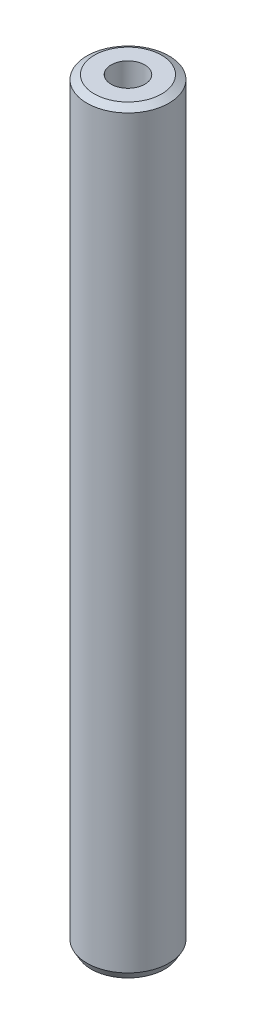
SolidWorks part; units mm, degrees
ref_plane "Front Plane" through (0, 0, 0) normal (0, 0, 1) x (1, 0, 0)
ref_plane "Top Plane" through (0, 0, 0) normal (0, 1, 0) x (1, 0, 0)
ref_plane "Right Plane" through (0, 0, 0) normal (1, 0, 0) x (0, 0, -1)
sketch "Sketch1" plane through (0, 0, 0) normal (0, 1, 0) x (1, 0, 0)
  circle A0 centre (0, 0) radius 20
  dimension "SHAFT_OD" = 40
extrude "Boss-Extrude1" add sketch "Sketch1" along normal blind 368.7275
sketch "Sketch2" plane through (0, 0, 0) normal (0, 1, 0) x (1, 0, 0)
  circle A0 centre (0, 0) radius 8.201
  dimension "BORE_D" = 16.402
extrude "Cut-Extrude1" cut sketch "Sketch2" along normal through all
chamfer "Chamfer1" distance 2.0804 angle 60 2 edges at (0, 368.7275, 20) (0, 0, 20) first distance on face at (0, 368.7275, 20) first distance on face at (0, 0, 8.201)
